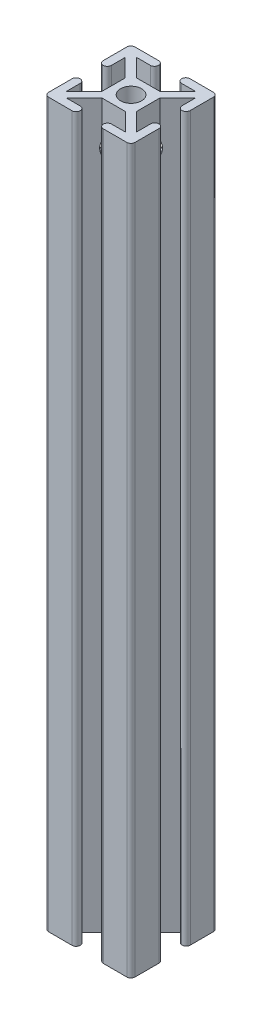
SolidWorks part; units mm, degrees
ref_plane "Alzado" through (0, 0, 0) normal (0, 0, 1) x (1, 0, 0)
ref_plane "Planta" through (0, 0, 0) normal (0, 1, 0) x (1, 0, 0)
ref_plane "Vista lateral" through (0, 0, 0) normal (1, 0, 0) x (0, 0, -1)
sketch "Croquis1" plane through (0, 0, 0) normal (0, 1, 0) x (1, 0, 0)
  line L0 (13.7955, 10.9364) -> (13.7955, 12.3614) construction
  line L1 (32.8484, -5.2136) -> (37.5734, -5.2136)
  line L2 (12.3705, 20.5113) -> (12.3705, 12.3614)
  line L3 (13.7955, 21.9363) -> (21.9455, 21.9363)
  line L4 (32.7955, 21.9363) -> (40.9455, 21.9363)
  line L5 (17.2734, -5.2136) -> (21.9984, -5.2136)
  line L6 (21.3705, 10.9364) -> (21.3705, 2.9364)
  line L7 (12.4234, 1.5114) -> (12.4234, -6.6386)
  line L8 (13.822, -8.0372) -> (21.9984, -8.0636)
  line L9 (42.3705, 20.5113) -> (42.3705, 12.4651)
  line L10 (15.2205, 17.0864) -> (15.2205, 12.3614)
  line L11 (42.3705, 1.6151) -> (42.3705, -6.6386)
  line L12 (23.3705, 20.5113) -> (21.9455, 20.5113) construction
  line L13 (32.8484, -8.0636) -> (40.9455, -8.0636)
  line L14 (17.2205, 19.0863) -> (21.9455, 19.0863)
  line L15 (15.2205, 1.5114) -> (15.2205, -3.2136)
  line L16 (31.3705, 20.5113) -> (32.7955, 20.5113) construction
  line L17 (32.7955, 19.0863) -> (37.5205, 19.0863)
  line L18 (40.9455, 11.0401) -> (40.9455, 12.4651) construction
  line L19 (23.3705, 12.9363) -> (17.2205, 19.0863)
  line L20 (39.5205, 17.0863) -> (39.5205, 12.4651)
  line L21 (40.9455, 3.0401) -> (40.9455, 1.6151) construction
  line L22 (21.3705, 10.9364) -> (15.2205, 17.0864)
  line L23 (39.5205, 1.6151) -> (39.5205, -3.2137)
  line L24 (31.4234, -6.6386) -> (32.8484, -6.6386) construction
  line L25 (21.3705, 2.9364) -> (15.2205, -3.2136)
  line L26 (23.3705, 12.9363) -> (31.3705, 12.9363)
  line L27 (31.3705, 12.9363) -> (37.5205, 19.0863)
  line L28 (13.822, 2.9364) -> (13.822, 1.5114) construction
  line L29 (17.2734, -5.2136) -> (23.4234, 0.9364)
  line L30 (23.4234, 0.9364) -> (31.4234, 0.9364)
  line L31 (31.4234, 0.9364) -> (37.5734, -5.2136)
  line L32 (23.4234, -6.6386) -> (21.9984, -6.6386) construction
  line L33 (33.3705, 2.9363) -> (39.5205, -3.2137)
  line L34 (33.3705, 10.9363) -> (39.5205, 17.0863)
  line L35 (33.3705, 10.9363) -> (33.3705, 2.9363)
  circle A0 centre (27.4234, 6.9364) radius 3.645
  arc A1 (12.3705, 12.3614) -> (15.2205, 12.3614) centre (13.7955, 12.3614) ccw
  arc A2 (21.9455, 19.0863) -> (21.9455, 21.9363) centre (21.9455, 20.5113) ccw
  arc A3 (32.7955, 21.9363) -> (32.7955, 19.0863) centre (32.7955, 20.5113) ccw
  arc A4 (39.5205, 12.4651) -> (42.3705, 12.4651) centre (40.9455, 12.4651) ccw
  arc A5 (42.3705, 1.6151) -> (39.5205, 1.6151) centre (40.9455, 1.6151) ccw
  arc A6 (32.8484, -5.2136) -> (32.8484, -8.0636) centre (32.8484, -6.6386) ccw
  arc A7 (15.2205, 1.5114) -> (12.4234, 1.5114) centre (13.822, 1.5114) ccw
  arc A8 (21.9984, -8.0636) -> (21.9984, -5.2136) centre (21.9984, -6.6386) ccw
  arc A9 (12.4234, -6.6386) -> (13.822, -8.0372) centre (13.822, -6.6386) ccw
  arc A10 (40.9455, -8.0636) -> (42.3705, -6.6386) centre (40.9455, -6.6386) ccw
  arc A11 (42.3705, 20.5113) -> (40.9455, 21.9363) centre (40.9455, 20.5113) ccw
  arc A12 (13.7955, 21.9363) -> (12.3705, 20.5113) centre (13.7955, 20.5113) ccw
  dimension "D1" = 7.29
  dimension "D2" = 1.425
  dimension "D3" = 1.425
  dimension "D4" = 1.425
  dimension "D5" = 1.425
  dimension "D6" = 1.425
  dimension "D7" = 1.425
  dimension "D8" = 1.425
  dimension "D9" = 1.425
extrude "Saliente-Extruir1" add sketch "Croquis1" along normal blind 200
sketch "Croquis3" plane through (0, 200, 0) normal (0, 1, 0) x (1, 0, 0)
extrude "Saliente-Extruir2" add sketch "Croquis1<2>" along normal blind 250
sketch "Croquis1<2>" plane through (0, 0, 0) normal (0, 1, 0) x (1, 0, 0) same geometry as "Croquis1"
sketch "Sketch1" plane through (0, 0, -12.9363) normal (0, 0, -1) x (-1, 0, 0)
  circle A0 centre (-27.3353, 235) radius 6.5
extrude "Cut-Extrude1" cut sketch "Sketch1" against normal blind 12
sketch "Sketch2" plane through (33.3705, 0, 0) normal (1, 0, 0) x (0, 0, -1)
  circle A0 centre (7, 235) radius 6.4942
extrude "Cut-Extrude2" cut sketch "Sketch2" against normal blind 12
sketch "Sketch3" plane through (0, 0, -12.9363) normal (0, 0, -1) x (-1, 0, 0)
  circle A0 centre (-27.4234, 55) radius 4
  dimension "D1" = 8
extrude "Cut-Extrude3" cut sketch "Sketch3" against normal blind 12
sketch "Sketch4" plane through (21.3705, 0, 0) normal (-1, 0, 0) x (0, 0, 1)
  circle A0 centre (-6.9892, 55) radius 4
  dimension "D1" = 8
extrude "Cut-Extrude4" cut sketch "Sketch4" against normal blind 12
